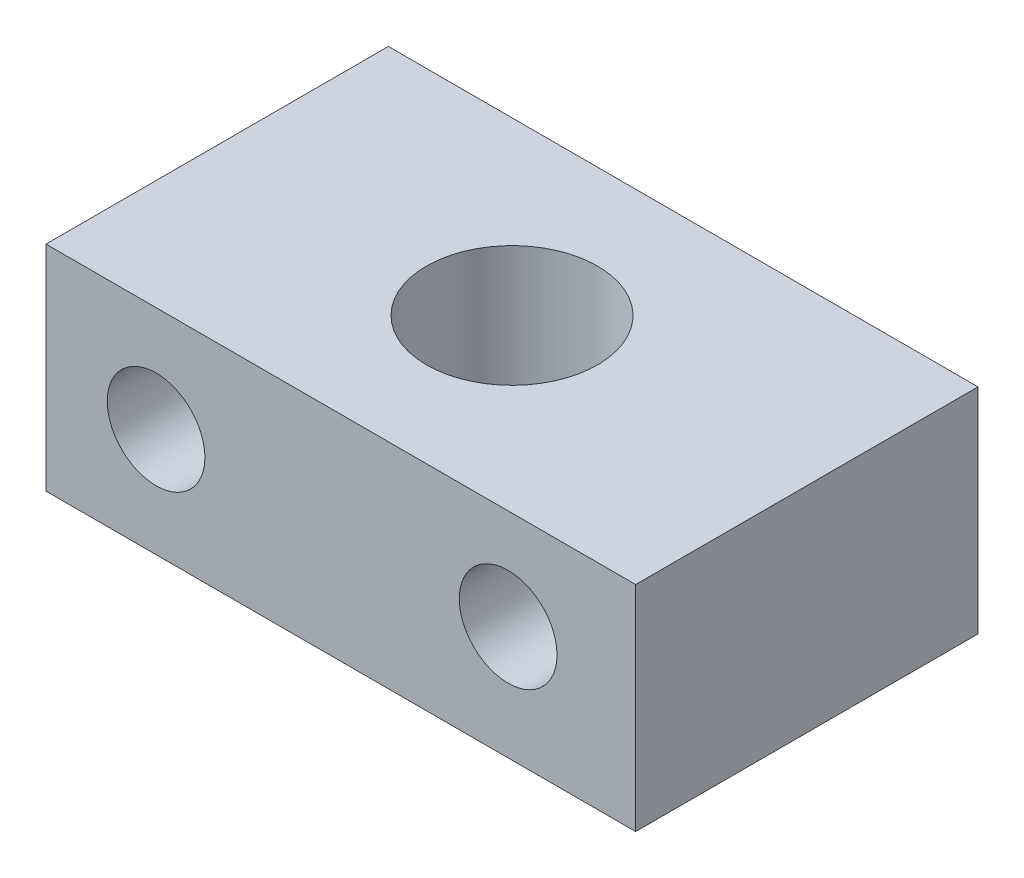
SolidWorks part; units mm, degrees
ref_plane "Front Plane" through (0, 0, 0) normal (0, 0, 1) x (1, 0, 0)
ref_plane "Top Plane" through (0, 0, 0) normal (0, 1, 0) x (1, 0, 0)
ref_plane "Right Plane" through (0, 0, 0) normal (1, 0, 0) x (0, 0, -1)
sketch "Sketch2" plane through (0, 0, 0) normal (0, 1, 0) x (1, 0, 0)
  line L1 (0, 0) -> (35, 0)
  line L2 (0, 0) -> (0, 20.32)
  line L3 (0, 20.32) -> (35, 20.32)
  line L4 (35, 0) -> (35, 20.32)
  circle A0 centre (17.5, 10.16) radius 5.08
  point P7 (0, 0)
  point P8 (17.5, 20.32)
  point P9 (0, 10.16)
  dimension "D3" = 10.16
  dimension "D1" = 35
  dimension "D2" = 20.32
extrude "Boss-Extrude1" add sketch "Sketch2" along normal blind 12.7
hole_wizard "M5 Clearance Hole1" positions "Sketch3" profile "Sketch4" hole size "M5" standard "ANSI Metric" end condition through all
sketch "Sketch3" plane through (0, 0, 0) normal (0, 0, 1) x (1, 0, 0)
  line L0 (0, 6.35) -> (35, 6.8533) construction
  line L1 (0, 12.7) -> (0, 0) construction
  line L2 (35, 12.7) -> (35, 0) construction
  point P0 (6.5331, 6.4439)
  point P2 (27.4308, 6.7445)
  point P13 (6.5331, 6.4439)
  point P14 (27.4308, 6.7445)
sketch "Sketch4" plane through (6.5331, 6.4439, 0) normal (1, 0, 0) x (0, -1, 0)
  line L0 (0, 0) -> (0, 20.32)
  line L1 (0, 20.32) -> (2.9, 20.32)
  line L2 (2.9, 20.32) -> (2.9, 0)
  line L5 (2.9, 0) -> (0, 0)
  line L11 (0, -6.35) -> (0, 107.95) construction
  dimension "Thru Hole Dia." = 5.8
  dimension "Thru Hole Depth" = 20.32
equation "\"press fit\"= 0.3mm"
